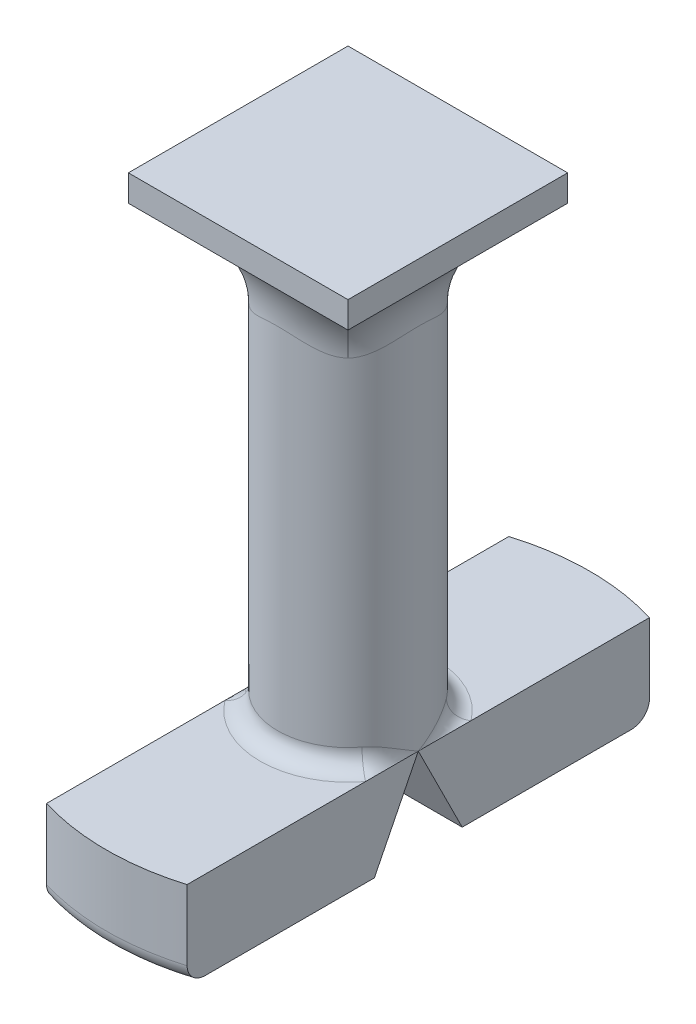
SolidWorks part; units mm, degrees
ref_plane "Front Plane" through (0, 0, 0) normal (0, 0, 1) x (1, 0, 0)
ref_plane "Top Plane" through (0, 0, 0) normal (0, 1, 0) x (1, 0, 0)
ref_plane "Right Plane" through (0, 0, 0) normal (1, 0, 0) x (0, 0, -1)
sketch "Sketch1" plane through (0, 0, 0) normal (0, 1, 0) x (1, 0, 0)
  line L0 (0, 27.5) -> (0, -27.5) construction
  line L1 (-8, 26.3106) -> (-8, -26.3106)
  line L2 (8, 26.3106) -> (8, -26.3106)
  arc A0 (-8, -26.3106) -> (8, -26.3106) centre (0, 0) ccw
  circle A1 centre (0, 0) radius 24 construction
  arc A2 (8, 26.3106) -> (-8, 26.3106) centre (0, 0) ccw
  dimension "D1" = 55
  dimension "D2" = 3.5
  dimension "D3" = 8
extrude "Boss-Extrude1" add sketch "Sketch1" along normal blind 10
sketch "Sketch2" plane through (0, 10, 0) normal (0, 1, 0) x (1, 0, 0)
  circle A0 centre (0, 0) radius 8
extrude "Boss-Extrude2" add sketch "Sketch2" along normal blind 50
sketch "Sketch3" plane through (0, 60, 0) normal (0, 1, 0) x (1, 0, 0)
  line L1 (-12.5, 12.5) -> (12.5, 12.5)
  line L2 (-12.5, 12.5) -> (-12.5, -12.5)
  line L3 (-12.5, -12.5) -> (12.5, -12.5)
  line L4 (12.5, 12.5) -> (12.5, -12.5)
  line L5 (-12.5, 12.5) -> (12.5, -12.5) construction
  line L6 (-12.5, -12.5) -> (12.5, 12.5) construction
  point P0 (0, 0)
  dimension "D1" = 25
  dimension "D2" = 25
extrude "Boss-Extrude3" add sketch "Sketch3" along normal blind 3
fillet "Fillet1" radius 9.6 1 edges at (0, 60, 8)
sketch "Sketch4" plane through (-8, 0, 0) normal (-1, 0, 0) x (0, 0, 1)
  line L0 (0, 10) -> (0, 0) construction
  line L1 (-26.3106, 0) -> (26.3106, 0) construction
  line L2 (-5, 0) -> (0, 10)
  line L3 (0, 10) -> (5, 0)
  line L4 (-5, 0) -> (5, 0)
  dimension "D1" = 5
  dimension "D2" = 5
extrude "Cut-Extrude1" cut sketch "Sketch4" against normal through all and the other way through all
fillet "Fillet2" radius 2 4 edges at (0, 10, -8) (0, 10, 8) (0, 0, -27.5) (0, 0, 27.5)
